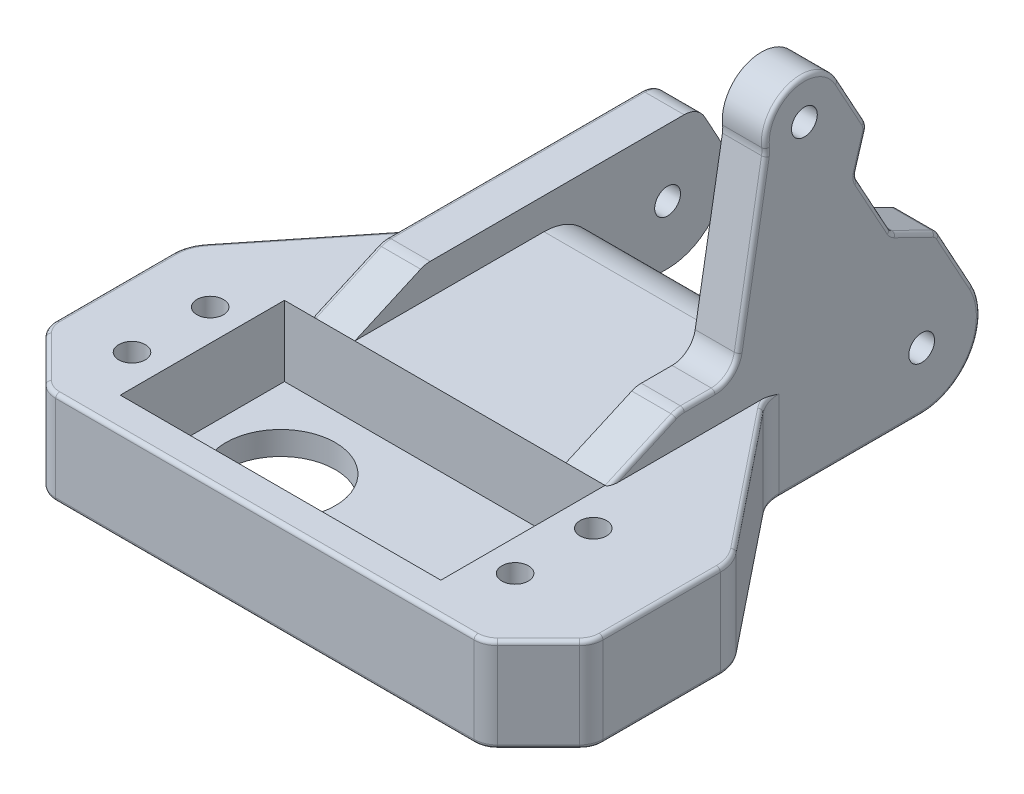
SolidWorks part; units mm, degrees
ref_plane "Front Plane" through (0, 0, 0) normal (0, 0, 1) x (1, 0, 0)
ref_plane "Top Plane" through (0, 0, 0) normal (0, 1, 0) x (1, 0, 0)
ref_plane "Right Plane" through (0, 0, 0) normal (1, 0, 0) x (0, 0, -1)
sketch "Sketch1" plane through (0, 0, 0) normal (1, 0, 0) x (0, 0, -1)
  line L0 (0, 0) -> (-15, 0) construction
  line L1 (-15, 32.5) -> (-15, 0) construction
  line L2 (0, -7.5) -> (-40, -7.5)
  line L3 (-40, -7.5) -> (-40, 4.5)
  line L25 (-10.6176, 34.9072) -> (6.5736, 3.6109)
  line L31 (-40, 4.5) -> (-31, 8.5)
  line L32 (-31, 8.5) -> (-23.899, 8.5)
  line L33 (-15, 32.5) -> (0, 0) construction
  line L34 (-23.899, 8.5) -> (-19.899, 31.5)
  circle A0 centre (0, 0) radius 1.65
  circle A1 centre (-15, 32.5) radius 1.65
  circle A2 centre (0, 0) radius 7.5
  circle A3 centre (-15, 32.5) radius 5
  dimension "D1" = 3.3
  dimension "D14" = 15
  dimension "D19" = 10
  dimension "D2" = 15
  dimension "D3" = 32.5
  dimension "D4" = 40
  dimension "D5" = 12
  dimension "D6" = 9
  dimension "D7" = 16
  dimension "D8" = 4
  dimension "D20" = 35.7946
  dimension "D22" = 1
extrude "Boss-Extrude1" add sketch "Sketch1" along normal mid plane 5.5 contours A3 L32 L31 A2 L25 | A2 A0 | A3 A1 region at (0, 7.9549, 17.3927) region at (0, 3.7109, 6.2723) region at (0, 33.7075, 10.2939)
sketch "Sketch2" plane through (2.75, 0, 0) normal (1, 0, 0) x (0, 0, -1)
  line L0 (0, 0) -> (-15, 32.5) construction
  line L1 (-7.5, 16.25) -> (-12.0398, 14.1547) construction
  line L5 (2.1027, 11.75) -> (-3.7402, 14.5979)
  line L6 (-10.6176, 34.9072) -> (6.5736, 3.6109) construction
  line L7 (-3.7402, 14.5979) -> (-8.4237, 23.1242)
  line L8 (-8.4237, 23.1242) -> (-6.9059, 28.15)
  line L9 (-6.9059, 28.15) -> (2.1027, 11.75)
  dimension "D3" = 5
  dimension "D4" = 3.75
  dimension "D5" = 4.35
  dimension "D6" = 11.75
  dimension "D7" = 6.5
  dimension "D8" = 5.25
extrude "Cut-Extrude1" cut sketch "Sketch2" against normal blind 10
fillet "Fillet3" radius 1.5 4 edges at (0, 11.75, -2.1027) (0, 14.5979, 3.7402) (0, 23.1242, 8.4237) (0, 28.15, 6.9059)
sketch "草图2" plane through (-2.75, 0, 0) normal (-1, 0, 0) x (0, 0, 1)
  line L0 (40, -7.5) -> (4.9749, -7.5)
  line L1 (40, -7.5) -> (40, 4.5)
  line L2 (40, 4.5) -> (15.8035, 4.5)
  arc A2 (4.9749, -7.5) -> (8.8895, -1.4063) centre (0, 0) ccw
  arc A3 (15.8035, 4.5) -> (8.8895, -1.4063) centre (15.8035, -2.5) ccw
  dimension "D1" = 18
  dimension "D2" = 7
extrude "凸台-拉伸1" add sketch "草图2" along normal blind 27
sketch "草图4" plane through (-29.75, 0, 0) normal (-1, 0, 0) x (0, 0, 1)
  line L0 (31, 8.5) -> (-3.8879, 8.5)
  line L1 (31, 8.5) -> (23.899, 8.5) construction
  line L6 (40, 4.5) -> (31, 8.5)
  line L7 (40, 4.5) -> (31, 8.5) construction
  line L10 (-2.332, 11.3325) -> (-6.5736, 3.6109)
  line L11 (3.312, 14.3892) -> (-1.6745, 11.9587)
  line L12 (8.1202, 22.5717) -> (3.9695, 15.0154)
  line L13 (7.0881, 27.5466) -> (8.2414, 23.7276)
  line L14 (10.6176, 34.9072) -> (7.2093, 28.7024)
  line L15 (23.899, 8.5) -> (19.899, 31.5)
  line L16 (31, 8.5) -> (23.899, 8.5)
  line L17 (40, 4.5) -> (31, 8.5)
  line L18 (40, -7.5) -> (40, 4.5)
  line L19 (0, -7.5) -> (40, -7.5)
  line L20 (-3.8879, 8.5) -> (-6.5736, 3.6109)
  line L28 (40, -7.5) -> (40, 4.5)
  line L29 (0, -7.5) -> (40, -7.5)
  circle A0 centre (0, 0) radius 1.65 construction
  circle A1 centre (0, 0) radius 1.65
  arc A6 (-1.6745, 11.9587) -> (-2.332, 11.3325) centre (-1.0173, 10.6103) ccw
  arc A7 (3.312, 14.3892) -> (3.9695, 15.0154) centre (2.6548, 15.7376) ccw
  arc A8 (8.1202, 22.5717) -> (8.2414, 23.7276) centre (6.8055, 23.2939) ccw
  arc A9 (7.2093, 28.7024) -> (7.0881, 27.5466) centre (8.524, 27.9803) ccw
  arc A10 (19.899, 31.5) -> (10.6176, 34.9072) centre (15, 32.5) ccw
  arc A11 (-6.5736, 3.6109) -> (0, -7.5) centre (0, 0) ccw
  arc A17 (-6.5736, 3.6109) -> (0, -7.5) centre (0, 0) ccw
  dimension "D1" = 0
extrude "凸台-拉伸2" add sketch "草图4" along normal blind 5.5
fillet "圆角1" radius 3 5 edges at (0, 31.5, 19.899) (0, 8.5, 31) (-32.5, 8.5, -3.8879) (0, 8.5, 23.899) (-32.5, 8.5, 31)
sketch "草图5" plane through (0, -7.5, 0) normal (0, -1, 0) x (1, 0, 0)
  line L0 (2.75, 20) -> (18.75, 40)
  line L1 (2.75, 0) -> (2.75, 40) construction
  line L2 (18.75, 40) -> (18.75, 65)
  line L3 (18.75, 65) -> (-51.25, 65)
  line L4 (-51.25, 65) -> (-51.25, 40)
  line L5 (-51.25, 40) -> (-35.25, 20)
  line L6 (-35.25, 0) -> (-35.25, 40) construction
  line L7 (-35.25, 20) -> (2.75, 20)
  line L8 (2.75, 40) -> (-35.25, 40) construction
  point P12 (-16.25, 40)
  point P13 (-16.25, 65)
  dimension "D1" = 70
  dimension "D2" = 45
  dimension "D3" = 20
extrude "凸台-拉伸3" add sketch "草图5" against normal up to surface (12 mm away) up to face at (-16.25, 4.5, 27.9017)
sketch "草图6" plane through (0, -7.5, 0) normal (0, -1, 0) x (1, 0, 0)
  line L0 (18.75, 65) -> (-51.25, 65) construction
  circle A0 centre (-3.75, 50.5) radius 1.65
  circle A1 centre (-28.75, 50.5) radius 7
  point P6 (-16.25, 65)
  dimension "D4" = 3.3
  dimension "D5" = 14
  dimension "D1" = 25
  dimension "D2" = 12.5
  dimension "D3" = 14.5
extrude "切除-拉伸1" cut sketch "草图6" against normal blind 10
sketch "草图7" plane through (0, 4.5, 0) normal (0, 1, 0) x (1, 0, 0)
  line L0 (-51.25, -65) -> (18.75, -65) construction
  line L1 (-38.75, -40) -> (2.25, -40)
  line L2 (-38.75, -40) -> (-38.75, -61)
  line L3 (-38.75, -61) -> (2.25, -61)
  line L4 (2.25, -40) -> (2.25, -61)
  line L6 (-51.25, -40) -> (-51.25, -65) construction
  line L7 (18.75, -65) -> (18.75, -40) construction
  circle A0 centre (-42.75, -45.5) radius 1.7
  circle A1 centre (-42.75, -55.5) radius 1.7
  circle A2 centre (6.25, -45.5) radius 1.7
  circle A3 centre (6.25, -55.5) radius 1.7
  dimension "D5" = 3.4
  dimension "D6" = 3.4
  dimension "D7" = 3.4
  dimension "D8" = 3.4
  dimension "D1" = 4
  dimension "D2" = 12.5
  dimension "D3" = 16.5
  dimension "D4" = 21
  dimension "D9" = 5.5
  dimension "D10" = 4
  dimension "D11" = 4
  dimension "D12" = 10
extrude "切除-拉伸2" cut sketch "草图7" against normal blind 9
sketch "草图9" plane through (0, -4.5, 0) normal (0, 1, 0) x (1, 0, 0)
  circle A0 centre (-3.75, -50.5) radius 3
  dimension "D1" = 6
extrude "切除-拉伸3" cut sketch "草图9" against normal blind 1.5
sketch "草图11" plane through (0, -7.5, 0) normal (0, -1, 0) x (1, 0, 0)
  circle A4 centre (-42.75, 55.5) radius 3.5
  circle A5 centre (-42.75, 45.5) radius 3.5
  circle A6 centre (6.25, 55.5) radius 3.5
  circle A7 centre (6.25, 45.5) radius 3.5
  point P4 (0, 0)
  point P5 (0, 0)
  dimension "D1" = 7
  dimension "D2" = 7
  dimension "D3" = 7
  dimension "D4" = 7
extrude "切除-拉伸4" cut sketch "草图11" against normal blind 5
fillet "圆角2" radius 5 4 edges at (18.75, -1.5, 40) (2.75, -1.5, 20) (-35.25, -1.5, 20) (-51.25, -1.5, 40)
chamfer "倒角1" distance 7 angle 45 2 edges at (18.75, -1.5, 65) (-51.25, -1.5, 65)
fillet "圆角3" radius 3 4 edges at (-51.25, -1.5, 58) (-44.25, -1.5, 65) (18.75, -1.5, 58) (11.75, -1.5, 65)
fillet "圆角4" radius 0.5 55 edges at (2.75, 6.3707, 35.7909) (2.75, 8.4346, 30.9861) (2.75, 8.5, 28.3928) (2.75, 9.2041, 24.4912) (-35.25, 6.3707, 35.7909) (-35.25, 8.4346, 30.9861) (-35.25, 8.5, 14.1252) (-35.25, 8.082, -3.6406) (-35.25, 5.2776, -5.658) (-35.25, -3.8189, -6.4549) (-35.25, -7.5, 9.123) (-35.5319, -7.5, 19.9011) (-43.25, -7.5, 30) (-50.9681, -7.5, 40.0989) (-51.25, -7.5, 49.2556) (-51.0216, -7.5, 57.9054) (-47.75, -7.5, 61.5) (-44.1554, -7.5, 64.7716) (-16.25, -7.5, 65) (11.6554, -7.5, 64.7716) (15.25, -7.5, 61.5) (18.5216, -7.5, 57.9054) (18.75, -7.5, 49.2556) (18.4681, -7.5, 40.0989) (10.75, -7.5, 30) (3.0319, -7.5, 19.9011) (2.75, -7.5, 9.123) (2.75, -3.8189, -6.4549) (2.75, 7.4717, -4.4528) (2.75, 11.6965, -2.0518) (2.75, 13.174, 0.8187) (2.75, 14.6514, 3.6893) (2.75, 18.7936, 6.0449) (2.75, 23.1374, 8.2973) (2.75, 25.6371, 7.6648) (2.75, 28.1367, 7.0322) (2.75, 31.8048, 8.9135) (2.75, 37.258, 16.5367) (2.75, 31.4481, 19.941) (2.75, 20.9973, 21.7255) (-35.5319, 4.5, 19.9011) (-43.25, 4.5, 30) (-50.9681, 4.5, 40.0989) (-51.25, 4.5, 49.2556) (-51.0216, 4.5, 57.9054) (-47.75, 4.5, 61.5) (-44.1554, 4.5, 64.7716) (3.0319, 4.5, 19.9011) (10.75, 4.5, 30) (18.4681, 4.5, 40.0989) (18.75, 4.5, 49.2556) (18.5216, 4.5, 57.9054) (15.25, 4.5, 61.5) (11.6554, 4.5, 64.7716) (-16.25, 4.5, 65)
